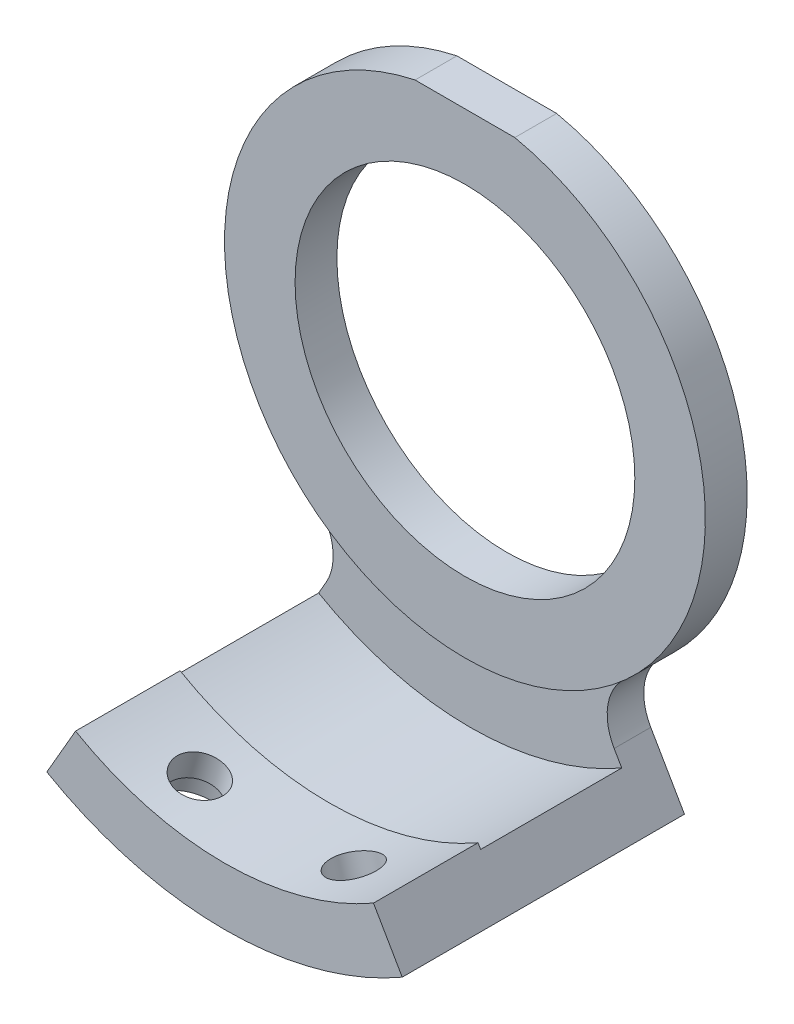
SolidWorks part; units mm, degrees
ref_plane "前视基准面" through (0, 0, 0) normal (0, 0, 1) x (1, 0, 0)
ref_plane "上视基准面" through (0, 0, 0) normal (0, 1, 0) x (1, 0, 0)
ref_plane "右视基准面" through (0, 0, 0) normal (1, 0, 0) x (0, 0, -1)
other "Configuration Table"
sketch "草图1" plane through (0, 0, 0) normal (0, 0, 1) x (1, 0, 0)
  line L0 (0, 30.7423) -> (0, -36.2878) construction
  circle A0 centre (0, 0) radius 23
  circle A1 centre (0, 0) radius 16.25
  point P10 (-15.1562, -24.7243)
  point P11 (-15.3535, -24.6022)
  point P12 (-12.375, -19.3871)
  point P13 (0, 0)
  point P14 (-13.629, -18.527)
  point P15 (-18.7426, -13.331)
  point P16 (-13.9705, -18.2709)
  dimension "D1" = 32.5
  dimension "D2" = 46
extrude "凸台-拉伸1" add sketch "草图1" along normal blind 4
sketch "草图2" plane through (0, 0, 0) normal (0, 0, 1) x (1, 0, 0)
  line L1 (-4.7697, 29.4965) -> (4.7697, 29.4965)
  line L2 (-4.7697, 29.4965) -> (-4.7697, 22.5)
  line L3 (-4.7697, 22.5) -> (4.7697, 22.5)
  line L4 (4.7697, 29.4965) -> (4.7697, 22.5)
  line L5 (-4.7697, 29.4965) -> (4.7697, 22.5) construction
  line L6 (-4.7697, 22.5) -> (4.7697, 29.4965) construction
  circle A0 centre (0, 0) radius 23 construction
  point P0 (0, 25.9982)
  point P7 (0, 0)
  dimension "D1" = 22.5
extrude "切除-拉伸1" cut sketch "草图2" along normal blind 14
sketch "草图3" plane through (0, 0, 0) normal (0, 0, 1) x (1, 0, 0)
  line L0 (0, 0) -> (-17, -29.4449)
  line L1 (0, 0) -> (0, -31.0659) construction
  line L2 (0, 0) -> (17, -29.4449)
  circle A0 centre (0, 0) radius 34
  arc A1 (-14.5, -25.1147) -> (14.5, -25.1147) centre (0, 0) ccw
  arc A2 (-4.7697, 22.5) -> (4.7697, 22.5) centre (0, 0) ccw construction
  arc A3 (-11.5, -19.9186) -> (4.7697, 22.5) centre (0, 0) ccw
  point P5 (0, 0)
  point P6 (-17, -29.4449)
  dimension "D2" = 58
  dimension "D3" = 68
  dimension "D1" = 30
extrude "凸台-拉伸2" add sketch "草图3" along normal blind 3.5 contours A3 L1 A1 L2 | L1 A3 L0 A1 region at (-6.6822, -24.9384, 0) region at (6.6822, -24.9384, 0)
extrude "凸台-拉伸3" add sketch "草图3<3>" along normal blind 27 contours A1 L0 A0 L2 region at (0, -30.1434, 0)
sketch "草图3<3>" plane through (0, 0, 0) normal (0, 0, 1) x (1, 0, 0) same geometry as "草图3"
fillet "圆角1" radius 5 2 edges at (-11.5, -19.9186, 1.75) (11.5, -19.9186, 1.75)
sketch "草图4" plane through (0, 0, 27) normal (0, 0, 1) x (1, 0, 0)
  line L2 (-17, -29.4449) -> (-14.25, -24.6817)
  line L3 (17, -29.4449) -> (14.1375, -24.4868)
  line L4 (13.775, -23.859) -> (14.5, -25.1147) construction
  arc A0 (-17, -29.4449) -> (17, -29.4449) centre (0, 0) ccw construction
  arc A1 (-17, -29.4449) -> (17, -29.4449) centre (0, 0) ccw
  circle A2 centre (0, 0) radius 28.5
  arc M1 (14.5, -25.1147) -> (-14.5, -25.1147) centre (0, 0) cw
  line M2 (-14.5, -25.1147) -> (-17, -29.4449)
  arc M3 (-17, -29.4449) -> (17, -29.4449) centre (0, 0) ccw
  line M4 (17, -29.4449) -> (14.5, -25.1147)
  dimension "D1" = 57
extrude "凸台-拉伸4" add sketch "草图4" against normal blind 10 contours M4 M1 M2 M3 | A2 L2 L3 M1 region at (0, -30.1434, 27) region at (-14.1211, -25.0448, 27)
ref_plane "基准面1" through (0, 0, 22) normal (0, 0, 1) x (1, 0, 0)
sketch "草图5" plane through (0, 0, 22) normal (0, 0, 1) x (1, 0, 0)
  line L0 (0, 0) -> (0, -39.7403) construction
  line L1 (0, 0) -> (-8.7998, -32.8415)
  line L2 (0, 0) -> (8.7998, -32.8415)
  arc A1 (-17, -29.4449) -> (17, -29.4449) centre (0, 0) ccw construction
  point P5 (-8.7998, -32.8415)
  point P8 (0, 0)
  point P9 (-7.3763, -27.5289)
  point P11 (0, 0)
  dimension "D1" = 15
hole_wizard "孔1" positions "3D草图1" profile "草图6" legacy end condition up to next
sketch3d "3D草图1"
  point P0 (-8.7998, -32.8415, 22)
  point P2 (8.7998, -32.8415, 22)
  point P5 (0, 0, 0)
  point P8 (0, 0, 0)
  point P10 (0, 0, 0)
sketch "草图6" plane through (-8.7998, -32.8415, 22) normal (0, 0, 1) x (0.9659, -0.2588, 0)
  line L0 (0, 0) -> (0, 5.5)
  line L1 (0, 5.5) -> (2.25, 5.5)
  line L2 (2.25, 5.5) -> (2.25, 3)
  line L3 (2.25, 3) -> (3.75, 3)
  line L4 (3.75, 3) -> (3.75, 0)
  line L5 (3.75, 0) -> (0, 0)
  line L6 (0, 110) -> (0, -10) construction
  dimension "直径" = 4.5
  dimension "深度" = 5.5
  dimension "柱坑直径" = 7.5
  dimension "柱坑深度" = 3
